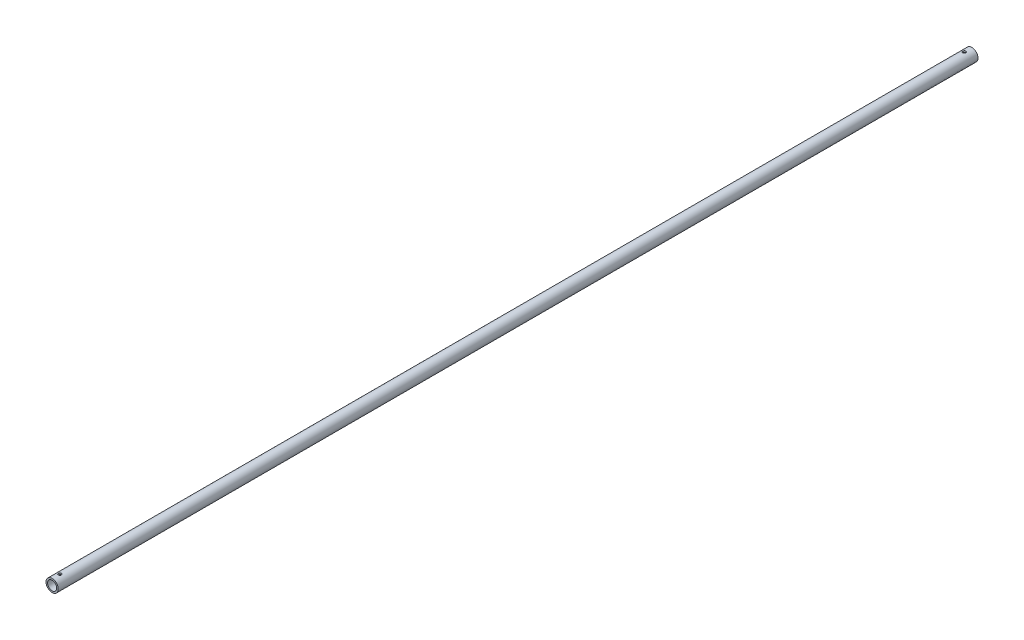
SolidWorks part; units mm, degrees
material "Thornel Mat VMA"
ref_plane "前视基准面" through (0, 0, 0) normal (0, 0, 1) x (1, 0, 0)
ref_plane "上视基准面" through (0, 0, 0) normal (0, 1, 0) x (1, 0, 0)
ref_plane "右视基准面" through (0, 0, 0) normal (1, 0, 0) x (0, 0, -1)
sketch "草图1" plane through (0, 0, 0) normal (0, 0, 1) x (1, 0, 0)
  circle A0 centre (0, 0) radius 3
  circle A1 centre (0, 0) radius 4
  dimension "D1" = 6
  dimension "D2" = 8
extrude "凸台-拉伸1" add sketch "草图1" along normal blind 300 and the other way blind 300
sketch "草图3" plane through (0, 0, 0) normal (0, 1, 0) x (1, 0, 0)
  line L0 (4, 300) -> (-4, 300) construction
  line L1 (-1000, 0) -> (49000, 0) construction
  circle A0 centre (0, 295) radius 1
  circle A1 centre (0, -295) radius 1
  dimension "D1" = 2
  dimension "D2" = 5
extrude "切除-拉伸2" cut sketch "草图3" against normal through all and the other way through all
sketch "草图6" plane through (0, 0, 0) normal (0, 1, 0) x (1, 0, 0)
  circle A0 centre (0, 0) radius 17.2534
